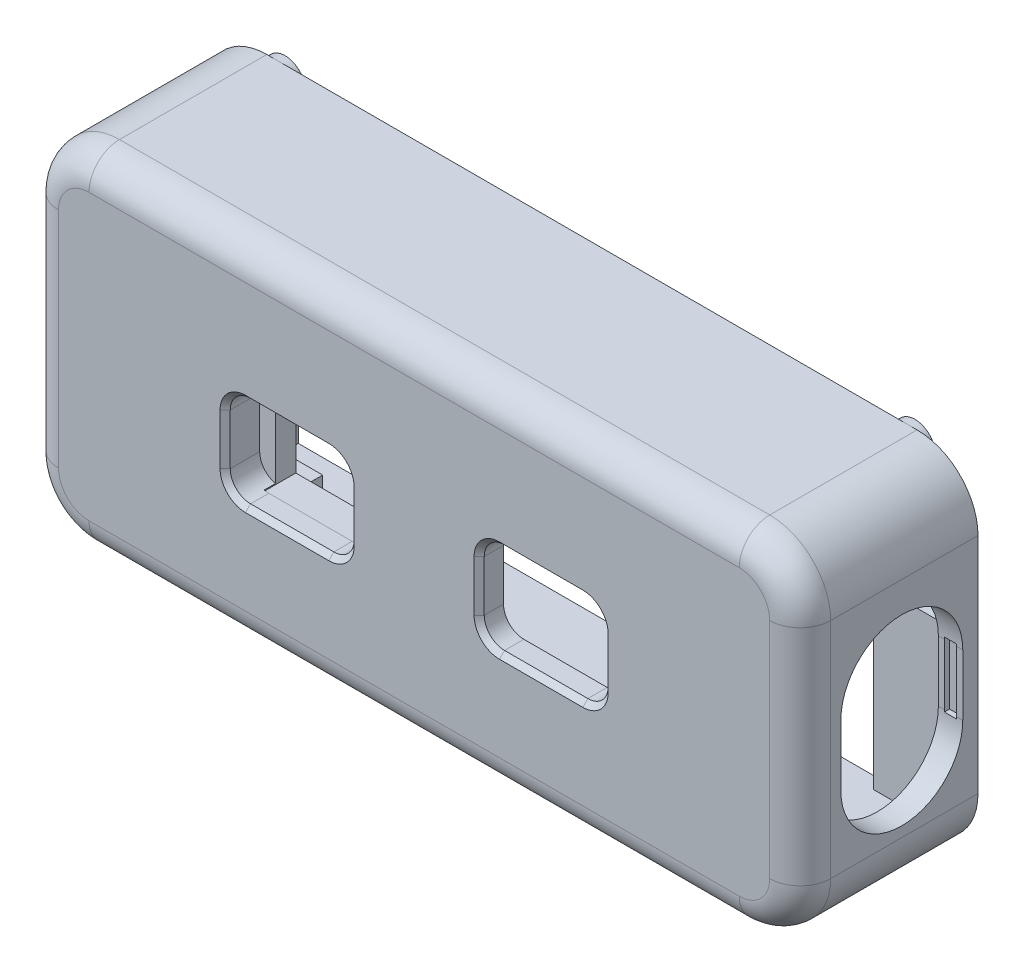
SolidWorks part; units mm, degrees
ref_plane "Front Plane" through (0, 0, 0) normal (0, 0, 1) x (1, 0, 0)
ref_plane "Top Plane" through (0, 0, 0) normal (0, 1, 0) x (1, 0, 0)
ref_plane "Right Plane" through (0, 0, 0) normal (1, 0, 0) x (0, 0, -1)
sketch "Sketch1" plane through (0, 0, 0) normal (0, 0, 1) x (1, 0, 0)
  line L0 (-32, 40) -> (32, 40)
  line L1 (38, 46) -> (38, 68)
  line L2 (32, 74) -> (-32, 74)
  line L3 (-38, 68) -> (-38, 46)
  arc A0 (-38, 46) -> (-32, 40) centre (-32, 46) ccw
  arc A1 (32, 40) -> (38, 46) centre (32, 46) ccw
  arc A2 (38, 68) -> (32, 74) centre (32, 68) ccw
  arc A3 (-32, 74) -> (-38, 68) centre (-32, 68) ccw
extrude "Boss-Extrude1" add sketch "Sketch1" along normal blind 17.5 from offset 80.8
fillet "Fillet1" radius 3 8 edges at (36.2426, 72.2426, 98.3) (38, 57, 98.3) (36.2426, 41.7574, 98.3) (0, 40, 98.3) (-36.2426, 41.7574, 98.3) (-38, 57, 98.3) (-36.2426, 72.2426, 98.3) (0, 74, 98.3)
sketch "Sketch2" plane through (0, 0, 0) normal (0, 0, 1) x (1, 0, 0)
  line L0 (-32, 42.4) -> (32, 42.4)
  line L1 (35.6, 46) -> (35.6, 68)
  line L2 (32, 71.6) -> (-32, 71.6)
  line L3 (-35.6, 68) -> (-35.6, 46)
  arc A0 (-35.6, 46) -> (-32, 42.4) centre (-32, 46) ccw
  arc A1 (32, 42.4) -> (35.6, 46) centre (32, 46) ccw
  arc A2 (35.6, 68) -> (32, 71.6) centre (32, 68) ccw
  arc A3 (-32, 71.6) -> (-35.6, 68) centre (-32, 68) ccw
extrude "Boss-Extrude2" add sketch "Sketch2" along normal blind 16.1 from offset 79.8 separate body
combine bodies "Combine1" operation type subtract main body 101 bodies to subtract 102
sketch "Sketch3" plane through (0, 0, 0) normal (0, 0, 1) x (1, 0, 0)
  line L1 (-36.1, 65.3) -> (-28.9, 65.3)
  line L2 (-36.1, 65.3) -> (-36.1, 71.61)
  line L3 (-36.1, 71.61) -> (-28.9, 71.61)
  line L4 (-28.9, 65.3) -> (-28.9, 71.61)
extrude "Boss-Extrude3" add sketch "Sketch3" along normal blind 6 from offset 80.8
sketch "Sketch4" plane through (0, 0, 0) normal (0, 1, 0) x (1, 0, 0)
  line L0 (-28.9, -86.8) -> (-36.1, -86.8)
  line L1 (-36.1, -86.8) -> (-36.1, -94)
  line L2 (-36.1, -94) -> (-28.9, -86.8)
extrude "Boss-Extrude4" add sketch "Sketch4" along normal blind 6.31 from offset 65.3
sketch "Sketch5" plane through (0, 0, 0) normal (0, 0, 1) x (1, 0, 0)
  line L1 (-35.61, 42.39) -> (-28.9, 42.39)
  line L2 (-35.61, 42.39) -> (-35.61, 60)
  line L3 (-35.61, 60) -> (-28.9, 60)
  line L4 (-28.9, 42.39) -> (-28.9, 60)
extrude "Boss-Extrude5" add sketch "Sketch5" along normal blind 1.2 from offset 80.8
sketch "Sketch6" plane through (0, 0, 0) normal (0, 0, 1) x (1, 0, 0)
  line L1 (-26, 42.39) -> (-22, 42.39)
  line L2 (-26, 42.39) -> (-26, 45.4)
  line L3 (-26, 45.4) -> (-22, 45.4)
  line L4 (-22, 42.39) -> (-22, 45.4)
extrude "Boss-Extrude6" add sketch "Sketch6" along normal blind 2 from offset 85.3
sketch "Sketch7" plane through (0, 0, 0) normal (0, 0, 1) x (1, 0, 0)
  line L1 (-26, 68.6) -> (-22, 68.6)
  line L2 (-26, 68.6) -> (-26, 71.61)
  line L3 (-26, 71.61) -> (-22, 71.61)
  line L4 (-22, 68.6) -> (-22, 71.61)
extrude "Boss-Extrude7" add sketch "Sketch7" along normal blind 2 from offset 85.3
sketch "Sketch8" plane through (0, 0, 0) normal (1, 0, 0) x (0, 0, -1)
  line L0 (-94.3, 53) -> (-94.3, 59)
  line L1 (-82.3, 59) -> (-82.3, 53)
  arc A0 (-82.3, 53) -> (-88.3, 47) centre (-88.3, 53) cw
  arc A1 (-88.3, 47) -> (-94.3, 53) centre (-88.3, 53) cw
  arc A2 (-94.3, 59) -> (-88.3, 65) centre (-88.3, 59) cw
  arc A3 (-88.3, 65) -> (-82.3, 59) centre (-88.3, 59) cw
extrude "Boss-Extrude8" add sketch "Sketch8" along normal blind 3.9 from offset 39 separate body offset against normal yes
combine bodies "Combine2" operation type subtract main body 108 bodies to subtract 109
sketch "Sketch9" plane through (0, 0, 0) normal (0, 0, 1) x (1, 0, 0)
  line L1 (-37.4, 52.8) -> (-36.2, 52.8)
  line L2 (-37.4, 52.8) -> (-37.4, 59.2)
  line L3 (-37.4, 59.2) -> (-36.2, 59.2)
  line L4 (-36.2, 52.8) -> (-36.2, 59.2)
extrude "Boss-Extrude9" add sketch "Sketch9" along normal blind 0.6 from offset 81.8 separate body
combine bodies "Combine3" operation type subtract main body 110 bodies to subtract 111
sketch "Sketch10" plane through (0, 0, 0) normal (0, 0, 1) x (1, 0, 0)
  line L1 (-37.4, 52.8) -> (-36.2, 52.8)
  line L2 (-37.4, 52.8) -> (-37.4, 59.2)
  line L3 (-37.4, 59.2) -> (-36.2, 59.2)
  line L4 (-36.2, 52.8) -> (-36.2, 59.2)
extrude "Boss-Extrude10" add sketch "Sketch10" along normal blind 0.6 from offset 94.2 separate body
combine bodies "Combine4" operation type subtract main body 112 bodies to subtract 113
sketch "Sketch11" plane through (0, 0, 0) normal (0, 0, 1) x (1, 0, 0)
  line L1 (28.9, 65.3) -> (36.1, 65.3)
  line L2 (28.9, 65.3) -> (28.9, 71.61)
  line L3 (28.9, 71.61) -> (36.1, 71.61)
  line L4 (36.1, 65.3) -> (36.1, 71.61)
extrude "Boss-Extrude11" add sketch "Sketch11" along normal blind 6 from offset 80.8
sketch "Sketch12" plane through (0, 0, 0) normal (0, 1, 0) x (1, 0, 0)
  line L0 (28.9, -86.8) -> (36.1, -86.8)
  line L1 (36.1, -86.8) -> (36.1, -94)
  line L2 (36.1, -94) -> (28.9, -86.8)
extrude "Boss-Extrude12" add sketch "Sketch12" along normal blind 6.31 from offset 65.3
sketch "Sketch13" plane through (0, 0, 0) normal (0, 0, 1) x (1, 0, 0)
  line L1 (28.9, 42.39) -> (35.61, 42.39)
  line L2 (28.9, 42.39) -> (28.9, 60)
  line L3 (28.9, 60) -> (35.61, 60)
  line L4 (35.61, 42.39) -> (35.61, 60)
extrude "Boss-Extrude13" add sketch "Sketch13" along normal blind 1.2 from offset 80.8
sketch "Sketch14" plane through (0, 0, 0) normal (0, 0, 1) x (1, 0, 0)
  line L1 (22, 42.39) -> (26, 42.39)
  line L2 (22, 42.39) -> (22, 45.4)
  line L3 (22, 45.4) -> (26, 45.4)
  line L4 (26, 42.39) -> (26, 45.4)
extrude "Boss-Extrude14" add sketch "Sketch14" along normal blind 2 from offset 85.3
sketch "Sketch15" plane through (0, 0, 0) normal (0, 0, 1) x (1, 0, 0)
  line L1 (22, 68.6) -> (26, 68.6)
  line L2 (22, 68.6) -> (22, 71.61)
  line L3 (22, 71.61) -> (26, 71.61)
  line L4 (26, 68.6) -> (26, 71.61)
extrude "Boss-Extrude15" add sketch "Sketch15" along normal blind 2 from offset 85.3
sketch "Sketch16" plane through (0, 0, 0) normal (1, 0, 0) x (0, 0, -1)
  line L0 (-94.3, 53) -> (-94.3, 59)
  line L1 (-82.3, 59) -> (-82.3, 53)
  arc A0 (-82.3, 53) -> (-88.3, 47) centre (-88.3, 53) cw
  arc A1 (-88.3, 47) -> (-94.3, 53) centre (-88.3, 53) cw
  arc A2 (-94.3, 59) -> (-88.3, 65) centre (-88.3, 59) cw
  arc A3 (-88.3, 65) -> (-82.3, 59) centre (-88.3, 59) cw
extrude "Boss-Extrude16" add sketch "Sketch16" along normal blind 3.9 from offset 35.1 separate body
combine bodies "Combine5" operation type subtract main body 119 bodies to subtract 120
sketch "Sketch17" plane through (0, 0, 0) normal (0, 0, 1) x (1, 0, 0)
  line L1 (36.2, 52.8) -> (37.4, 52.8)
  line L2 (36.2, 52.8) -> (36.2, 59.2)
  line L3 (36.2, 59.2) -> (37.4, 59.2)
  line L4 (37.4, 52.8) -> (37.4, 59.2)
extrude "Boss-Extrude17" add sketch "Sketch17" along normal blind 0.6 from offset 81.8 separate body
combine bodies "Combine6" operation type subtract main body 121 bodies to subtract 122
sketch "Sketch18" plane through (0, 0, 0) normal (0, 0, 1) x (1, 0, 0)
  line L1 (36.2, 52.8) -> (37.4, 52.8)
  line L2 (36.2, 52.8) -> (36.2, 59.2)
  line L3 (36.2, 59.2) -> (37.4, 59.2)
  line L4 (37.4, 52.8) -> (37.4, 59.2)
extrude "Boss-Extrude18" add sketch "Sketch18" along normal blind 0.6 from offset 94.2 separate body
combine bodies "Combine7" operation type subtract main body 123 bodies to subtract 124
sketch "Sketch19" plane through (0, 0, 0) normal (0, 0, 1) x (1, 0, 0)
  circle A0 centre (-31, 68.3) radius 2
extrude "Boss-Extrude19" add sketch "Sketch19" along normal blind 0.81 from offset 80
sketch "Sketch20" plane through (0, 0, 0) normal (0, 0, 1) x (1, 0, 0)
  circle A0 centre (-31, 68.3) radius 1
extrude "Boss-Extrude20" add sketch "Sketch20" along normal blind 8 from offset 79.8 separate body
combine bodies "Combine8" operation type subtract main body 126 bodies to subtract 127
sketch "Sketch21" plane through (0, 0, 0) normal (0, 0, 1) x (1, 0, 0)
  circle A0 centre (-31, 72) radius 2
extrude "Boss-Extrude21" add sketch "Sketch21" along normal blind 0.81 from offset 80
sketch "Sketch22" plane through (0, 0, 0) normal (0, 0, 1) x (1, 0, 0)
  circle A0 centre (-31, 72) radius 1
extrude "Boss-Extrude22" add sketch "Sketch22" along normal blind 8 from offset 79.8 separate body
combine bodies "Combine9" operation type subtract main body 129 bodies to subtract 130
sketch "Sketch23" plane through (0, 0, 0) normal (0, 0, 1) x (1, 0, 0)
  circle A0 centre (31, 68.3) radius 2
extrude "Boss-Extrude23" add sketch "Sketch23" along normal blind 0.81 from offset 80
sketch "Sketch24" plane through (0, 0, 0) normal (0, 0, 1) x (1, 0, 0)
  circle A0 centre (31, 68.3) radius 1
extrude "Boss-Extrude24" add sketch "Sketch24" along normal blind 8 from offset 79.8 separate body
combine bodies "Combine10" operation type subtract main body 132 bodies to subtract 133
sketch "Sketch25" plane through (0, 0, 0) normal (0, 0, 1) x (1, 0, 0)
  circle A0 centre (31, 72) radius 2
extrude "Boss-Extrude25" add sketch "Sketch25" along normal blind 0.81 from offset 80
sketch "Sketch26" plane through (0, 0, 0) normal (0, 0, 1) x (1, 0, 0)
  circle A0 centre (31, 72) radius 1
extrude "Boss-Extrude26" add sketch "Sketch26" along normal blind 8 from offset 79.8 separate body
combine bodies "Combine11" operation type subtract main body 135 bodies to subtract 136
sketch "Sketch27" plane through (0, 0, 0) normal (0, 0, 1) x (1, 0, 0)
  line L1 (-19, 49.9) -> (-6, 49.9)
  line L2 (-19, 49.9) -> (-19, 62.9)
  line L3 (-19, 62.9) -> (-6, 62.9)
  line L4 (-6, 49.9) -> (-6, 62.9)
extrude "Boss-Extrude27" add sketch "Sketch27" along normal blind 3.01 from offset 92.9
sketch "Sketch28" plane through (0, 0, 0) normal (0, 0, 1) x (1, 0, 0)
  line L1 (-17.05, 51.85) -> (-7.95, 51.85)
  line L2 (-17.05, 51.85) -> (-17.05, 60.95)
  line L3 (-17.05, 60.95) -> (-7.95, 60.95)
  line L4 (-7.95, 51.85) -> (-7.95, 60.95)
extrude "Boss-Extrude28" add sketch "Sketch28" along normal blind 4.1 from offset 91.9 separate body
combine bodies "Combine12" operation type subtract main body 138 bodies to subtract 139
sketch "Sketch29" plane through (0, 0, 0) normal (0, 0, 1) x (1, 0, 0)
  line L1 (2.2, 42.39) -> (22.8, 42.39)
  line L2 (2.2, 42.39) -> (2.2, 48.6)
  line L3 (2.2, 48.6) -> (22.8, 48.6)
  line L4 (22.8, 42.39) -> (22.8, 48.6)
extrude "Boss-Extrude29" add sketch "Sketch29" along normal blind 2.51 from offset 93.4
sketch "Sketch30" plane through (0, 0, 0) normal (0, 0, 1) x (1, 0, 0)
  line L1 (1, 42.39) -> (2.2, 42.39)
  line L2 (1, 42.39) -> (1, 71.61)
  line L3 (1, 71.61) -> (2.2, 71.61)
  line L4 (2.2, 42.39) -> (2.2, 71.61)
extrude "Boss-Extrude30" add sketch "Sketch30" along normal blind 2.51 from offset 93.4
sketch "Sketch31" plane through (0, 0, 0) normal (0, 0, 1) x (1, 0, 0)
  line L1 (22.8, 42.39) -> (24, 42.39)
  line L2 (22.8, 42.39) -> (22.8, 71.61)
  line L3 (22.8, 71.61) -> (24, 71.61)
  line L4 (24, 42.39) -> (24, 71.61)
extrude "Boss-Extrude31" add sketch "Sketch31" along normal blind 2.51 from offset 93.4
sketch "Sketch32" plane through (0, 0, 0) normal (0, 0, 1) x (1, 0, 0)
  line L0 (-16.6, 51.9) -> (-8.4, 51.9)
  line L1 (-6.4, 53.9) -> (-6.4, 58.9)
  line L2 (-8.4, 60.9) -> (-16.6, 60.9)
  line L3 (-18.6, 58.9) -> (-18.6, 53.9)
  arc A0 (-18.6, 53.9) -> (-16.6, 51.9) centre (-16.6, 53.9) ccw
  arc A1 (-8.4, 51.9) -> (-6.4, 53.9) centre (-8.4, 53.9) ccw
  arc A2 (-6.4, 58.9) -> (-8.4, 60.9) centre (-8.4, 58.9) ccw
  arc A3 (-16.6, 60.9) -> (-18.6, 58.9) centre (-16.6, 58.9) ccw
extrude "Boss-Extrude32" add sketch "Sketch32" along normal blind 4.4 from offset 94.9 separate body
combine bodies "Combine13" operation type subtract main body 143 bodies to subtract 144
chamfer "Chamfer1" distance 0.5 angle 45 8 edges at (-12.5, 51.9, 98.3) (-18.0142, 52.4858, 98.3) (-6.9858, 52.4858, 98.3) (-18.6, 56.4, 98.3) (-6.4, 56.4, 98.3) (-18.0142, 60.3142, 98.3) (-6.9858, 60.3142, 98.3) (-12.5, 60.9, 98.3)
sketch "Sketch33" plane through (0, 0, 0) normal (0, 0, 1) x (1, 0, 0)
  line L0 (8.4, 51.9) -> (16.6, 51.9)
  line L1 (18.6, 53.9) -> (18.6, 58.9)
  line L2 (16.6, 60.9) -> (8.4, 60.9)
  line L3 (6.4, 58.9) -> (6.4, 53.9)
  arc A0 (6.4, 53.9) -> (8.4, 51.9) centre (8.4, 53.9) ccw
  arc A1 (16.6, 51.9) -> (18.6, 53.9) centre (16.6, 53.9) ccw
  arc A2 (18.6, 58.9) -> (16.6, 60.9) centre (16.6, 58.9) ccw
  arc A3 (8.4, 60.9) -> (6.4, 58.9) centre (8.4, 58.9) ccw
extrude "Boss-Extrude33" add sketch "Sketch33" along normal blind 4.4 from offset 94.9 separate body
combine bodies "Combine14" operation type subtract main body 145 bodies to subtract 146
chamfer "Chamfer2" distance 0.5 angle 45 8 edges at (12.5, 51.9, 98.3) (6.9858, 52.4858, 98.3) (18.0142, 52.4858, 98.3) (6.4, 56.4, 98.3) (18.6, 56.4, 98.3) (6.9858, 60.3142, 98.3) (18.0142, 60.3142, 98.3) (12.5, 60.9, 98.3)
